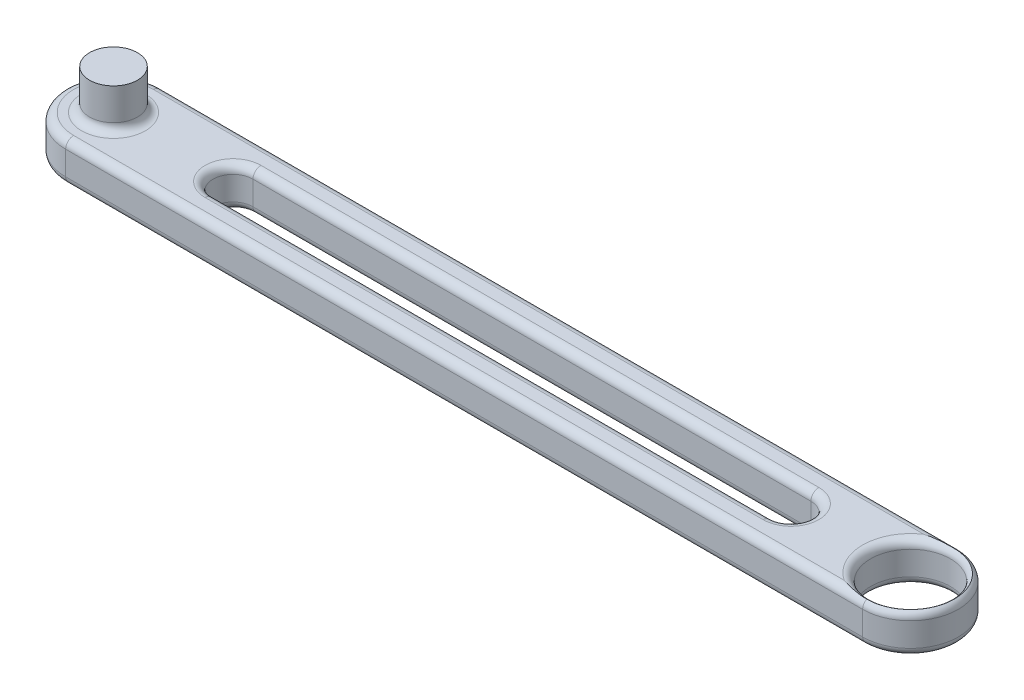
SolidWorks part; units mm, degrees
ref_plane "Front" through (0, 0, 0) normal (0, 0, 1) x (1, 0, 0)
ref_plane "Top" through (0, 0, 0) normal (0, 1, 0) x (1, 0, 0)
ref_plane "Right" through (0, 0, 0) normal (1, 0, 0) x (0, 0, -1)
sketch "草图1" plane through (0, 0, 0) normal (0, 1, 0) x (1, 0, 0)
  line L0 (-59.0043, 0) -> (63.069, 0) construction
  circle A0 centre (-40, 0) radius 6
  circle A1 centre (60, 0) radius 6
  dimension "D1" = 12
  dimension "D3" = 12
  dimension "D2" = 100
  dimension "D4" = 40
extrude "凸台-拉伸1" add sketch "草图1" along normal blind 5
sketch "草图3" plane through (0, 0, 0) normal (0, 1, 0) x (1, 0, 0)
  line L0 (-61.778, 0) -> (78.4405, 0) construction
  line L1 (0, 36.4306) -> (0, -33.6787) construction
  line L6 (-40, 6) -> (60, 6)
  line L7 (60, 6) -> (60, -6)
  line L8 (60, -6) -> (-40, -6)
  line L9 (-40, -6) -> (-40, 6)
  circle A2 centre (-40, 0) radius 6 construction
  circle A3 centre (60, 0) radius 6 construction
extrude "凸台-拉伸3" add sketch "草图3" along normal blind 5
sketch "草图4" plane through (0, 5, 0) normal (0, 1, 0) x (1, 0, 0)
  circle A0 centre (-40, 0) radius 3
  dimension "D1" = 6
sketch "草图5" plane through (0, 5, 0) normal (0, 1, 0) x (1, 0, 0)
  circle A0 centre (60, 0) radius 5
  dimension "D1" = 10
extrude "切除-拉伸2" cut sketch "草图5" against normal through all
sketch "草图6" plane through (0, 5, 0) normal (0, 1, 0) x (1, 0, 0)
  line L0 (-65.6937, 0) -> (69.5957, 0) construction
  circle A2 centre (-25, 0) radius 2.5
  circle A3 centre (45, 0) radius 2.5
  dimension "D3" = 5
  dimension "D4" = 5
  dimension "D1" = 25
  dimension "D2" = 45
extrude "切除-拉伸3" cut sketch "草图6" against normal through all
sketch "草图7" plane through (0, 5, 0) normal (0, 1, 0) x (1, 0, 0)
  line L4 (-25, 2.5) -> (45, 2.5)
  line L5 (45, 2.5) -> (45, -2.5)
  line L6 (45, -2.5) -> (-25, -2.5)
  line L7 (-25, -2.5) -> (-25, 2.5)
  circle A2 centre (-25, 0) radius 2.5 construction
  circle A3 centre (45, 0) radius 2.5 construction
extrude "切除-拉伸4" cut sketch "草图7" against normal through all
extrude "凸台-拉伸4" add sketch "草图4" along normal blind 5
fillet "圆角1" radius 1 1 edges at (-40, 5, 3)
fillet "圆角2" radius 1 18 edges at (-46, 5, 0) (10, 5, -6) (66, 5, 0) (10, 5, 6) (60, 5, 5) (-27.5, 5, 0) (10, 5, 2.5) (47.5, 5, 0) (10, 5, -2.5) (-46, 0, 0) (10, 0, 6) (66, 0, 0) (10, 0, -6) (60, 0, 5) (10, 0, 2.5) (-27.5, 0, 0) (10, 0, -2.5) (47.5, 0, 0)
